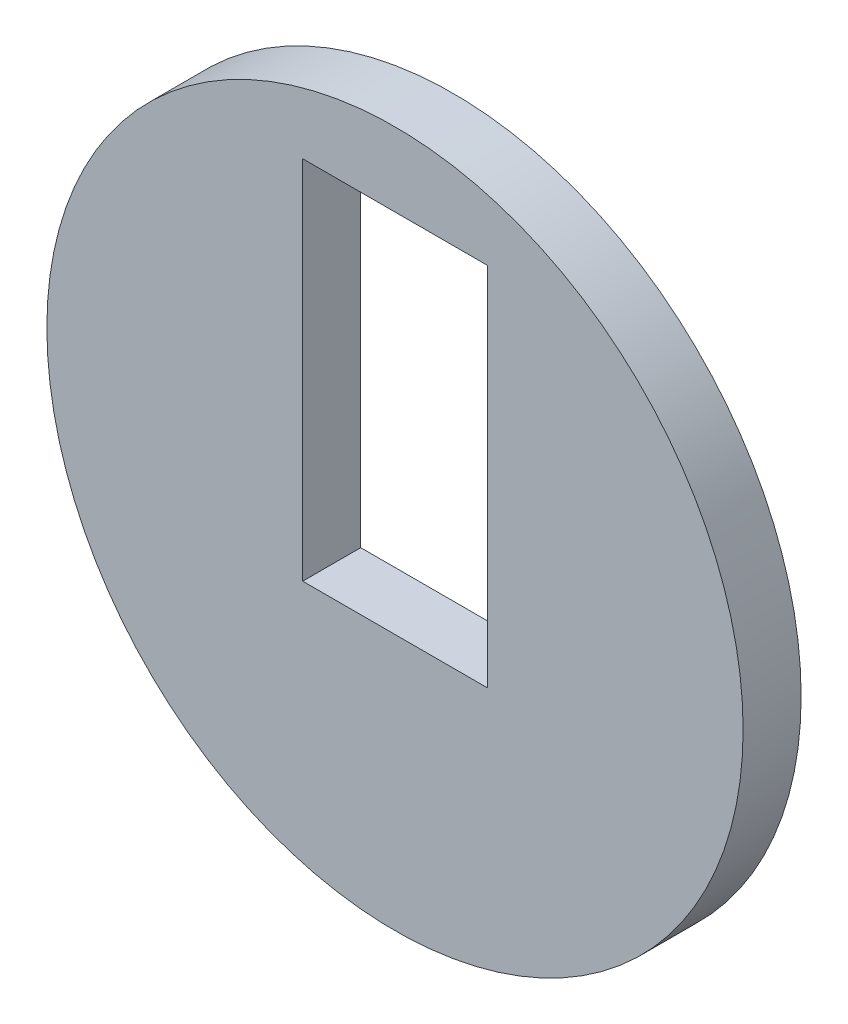
SolidWorks part; units mm, degrees
ref_plane "Front Plane" through (0, 0, 0) normal (0, 0, 1) x (1, 0, 0)
ref_plane "Top Plane" through (0, 0, 0) normal (0, 1, 0) x (1, 0, 0)
ref_plane "Right Plane" through (0, 0, 0) normal (1, 0, 0) x (0, 0, -1)
sketch "Sketch1" plane through (0, 0, 0) normal (0, 0, 1) x (1, 0, 0)
  circle A0 centre (0, 0) radius 38.1
extrude "Boss-Extrude1" add sketch "Sketch1" along normal blind 6.35
sketch "Sketch4" plane through (0, 0, 0) normal (0, 0, -1) x (-1, 0, 0)
  line L1 (-10.1, 30.02) -> (10.1, 30.02)
  line L2 (-10.1, 30.02) -> (-10.1, -10.02)
  line L3 (-10.1, -10.02) -> (10.1, -10.02)
  line L4 (10.1, 30.02) -> (10.1, -10.02)
  dimension "D1" = 10.02
  dimension "D2" = 30.02
  dimension "D3" = 10.1
  dimension "D4" = 10.1
extrude "Cut-Extrude1" cut sketch "Sketch4" against normal through all
